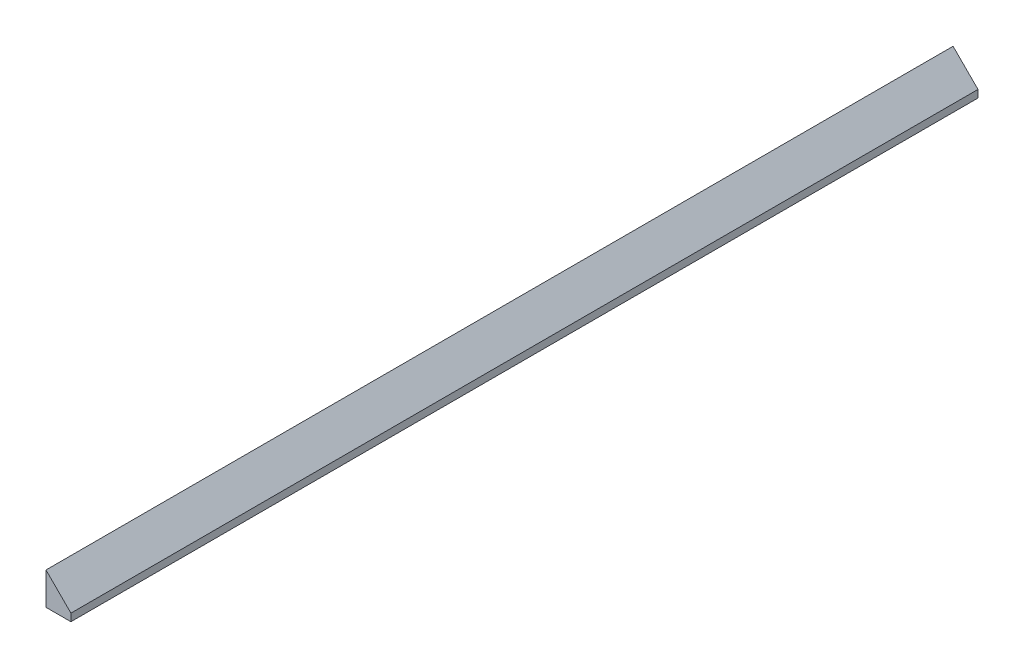
SolidWorks part; units mm, degrees
material "6061-T6 (SS)"
ref_plane "Front Plane" through (0, 0, 0) normal (0, 0, 1) x (1, 0, 0)
ref_plane "Top Plane" through (0, 0, 0) normal (0, 1, 0) x (1, 0, 0)
ref_plane "Right Plane" through (0, 0, 0) normal (1, 0, 0) x (0, 0, -1)
sketch "Sketch1" plane through (0, 0, 0) normal (0, 0, 1) x (1, 0, 0)
  line L5 (0, 0) -> (2.6, 0)
  line L6 (2.6, 0) -> (0, 2.6)
  line L7 (0, 2.6) -> (0, 0)
  line L11 (2, 0) -> (2, 0.6)
  dimension "D1" = 0.6
  dimension "D2" = 2.6
extrude "Boss-Extrude1" add sketch "Sketch1" against normal mid plane 72.8 contours L5 L11 L6 L7 region at (0.7917, 0.9042, 0)
